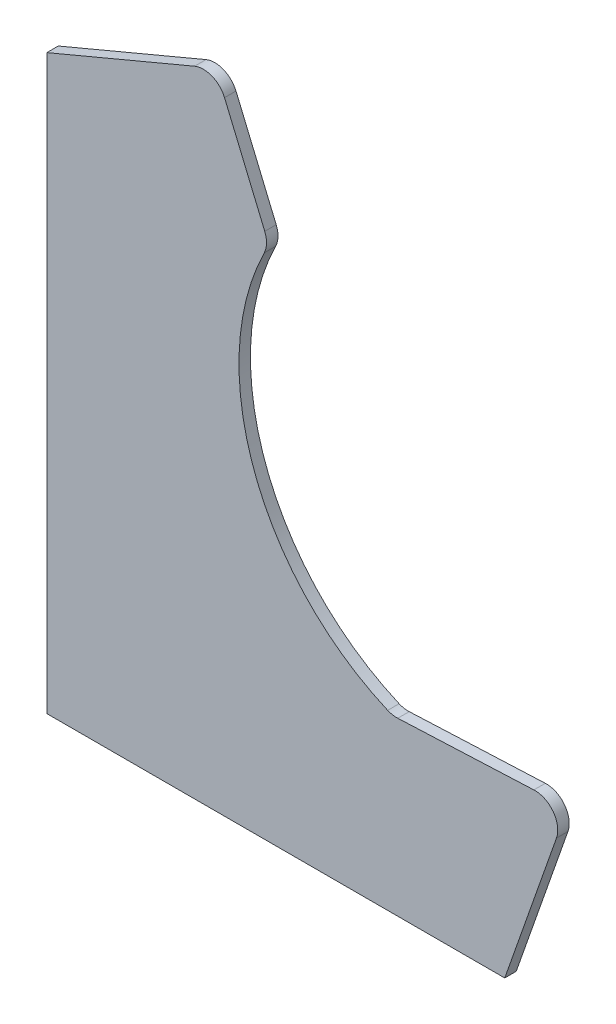
SolidWorks part; units mm, degrees
ref_plane "Plan de face" through (0, 0, 0) normal (0, 0, 1) x (1, 0, 0)
ref_plane "Plan de dessus" through (0, 0, 0) normal (0, 1, 0) x (1, 0, 0)
ref_plane "Plan de droite" through (0, 0, 0) normal (1, 0, 0) x (0, 0, -1)
sketch "Esquisse1" plane through (0, 0, 0) normal (0, 0, 1) x (1, 0, 0)
  line L0 (0, 0) -> (0, 500)
  line L1 (0, 0) -> (400, 0)
  line L2 (0, 500) -> (129.0626, 554.25)
  line L3 (155.25, 543.5626) -> (190.3729, 460.004)
  line L4 (400, 0) -> (445.1745, 128.385)
  line L5 (425.4268, 155.004) -> (306.5424, 149.7585)
  arc A0 (189.8854, 443.4335) -> (297.7533, 151.3687) centre (382.69, 348.69) ccw
  arc A1 (155.25, 543.5626) -> (129.0626, 554.25) centre (136.8126, 535.8126) ccw
  arc A2 (425.4268, 155.004) -> (445.1745, 128.385) centre (426.3084, 135.0234) cw
  arc A3 (189.8854, 443.4335) -> (190.3729, 460.004) centre (171.9355, 452.254) ccw
  arc A4 (306.5424, 149.7585) -> (297.7533, 151.3687) centre (305.6608, 169.7391) cw
  point P12 (147.5, 562)
  point P15 (455, 156.3088)
  point P18 (193.9979, 451.38)
  dimension "D13" = 20
  dimension "D14" = 20
  dimension "D15" = 20
  dimension "D7" = 20
  dimension "D1" = 400
  dimension "D2" = 500
  dimension "D3" = 62
  dimension "D4" = 147.5
  dimension "D5" = 110.62
  dimension "D6" = 455
  dimension "D8" = 119
  dimension "D10" = 382.69
  dimension "D11" = 348.69
extrude "Boss.-Extru.1" add sketch "Esquisse1" along normal blind 10
